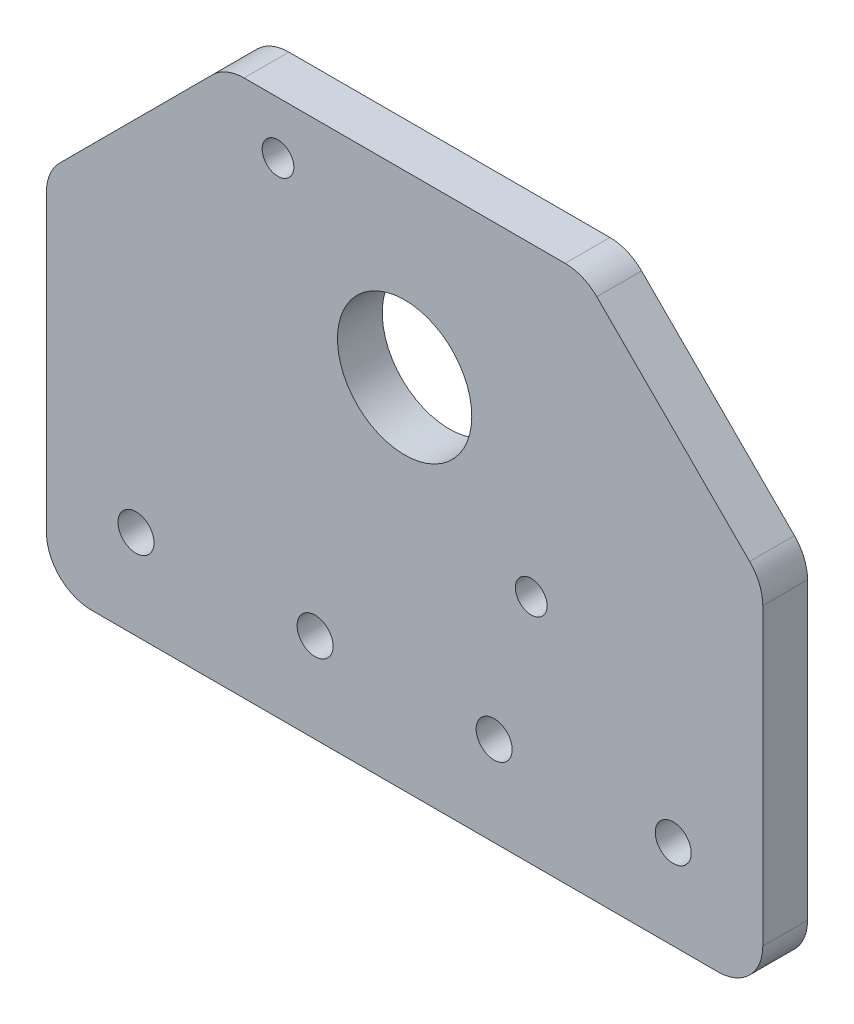
SolidWorks part; units mm, degrees
material "6061-T6 (SS)"
ref_plane "Front Plane" through (0, 0, 0) normal (0, 0, 1) x (1, 0, 0)
ref_plane "Top Plane" through (0, 0, 0) normal (0, 1, 0) x (1, 0, 0)
ref_plane "Right Plane" through (0, 0, 0) normal (1, 0, 0) x (0, 0, -1)
sketch "Sketch1" plane through (0, 0, 0) normal (0, 0, 1) x (1, 0, 0)
  line L0 (50.8, 25.4) -> (-50.8, 25.4)
  line L1 (-50.8, 25.4) -> (-50.8, -50.8)
  line L2 (-50.8, -50.8) -> (50.8, -50.8)
  line L3 (50.8, -50.8) -> (50.8, 25.4)
  circle A0 centre (0, 0) radius 9.525
  point P4 (0, -50.8)
  dimension "D1" = 19.05
  dimension "D2" = 25.4
  dimension "D3" = 76.2
  dimension "D4" = 101.6
extrude "Boss-Extrude1" add sketch "Sketch1" along normal mid plane 6.35
hole_wizard "#8 Clearance Hole1" positions "Sketch3" profile "Sketch2" hole size "#8" standard "ANSI Inch" end condition through all
sketch "Sketch3" plane through (0, 0, 3.175) normal (0, 0, 1) x (1, 0, 0)
  line L0 (-17.9605, 17.9605) -> (17.9605, -17.9605) construction
  line L2 (-50.8, -50.8) -> (50.8, -50.8) construction
  point P0 (-17.9605, 17.9605)
  point P2 (17.9605, -17.9605)
  dimension "D1" = 50.8
  dimension "D2" = 45
sketch "Sketch2" plane through (-17.9605, 17.9605, 3.175) normal (1, 0, 0) x (0, -1, 0)
  line L0 (0, 0) -> (0, 6.35)
  line L1 (0, 6.35) -> (2.2479, 6.35)
  line L2 (2.2479, 6.35) -> (2.2479, 0)
  line L5 (2.2479, 0) -> (0, 0)
  line L11 (0, -6.35) -> (0, 107.95) construction
  dimension "Thru Hole Dia." = 4.4958
  dimension "Thru Hole Depth" = 6.35
chamfer "Chamfer1" distance 25.4 angle 45 2 edges at (50.8, 25.4, 0) (-50.8, 25.4, 0)
hole_wizard "#10 Clearance Hole2" positions "Sketch5" profile "Sketch4" hole size "#10" standard "ANSI Inch" end condition through all
sketch "Sketch5" plane through (0, 0, 3.175) normal (0, 0, 1) x (1, 0, 0)
  line L0 (-50.8, -50.8) -> (50.8, -50.8) construction
  line L1 (-50.8, 0) -> (-50.8, -50.8) construction
  point P0 (-38.1, -38.1)
  point P12 (-12.7, -38.1)
  point P13 (12.7, -38.1)
  point P14 (38.1, -38.1)
  dimension "D1" = 12.7
  dimension "D2" = 12.7
  dimension "D4" = 25.4
  dimension "D3" = 4
sketch "Sketch4" plane through (-38.1, -38.1, 3.175) normal (1, 0, 0) x (0, -1, 0)
  line L0 (0, 0) -> (0, 6.35)
  line L1 (0, 6.35) -> (2.5527, 6.35)
  line L2 (2.5527, 6.35) -> (2.5527, 0)
  line L5 (2.5527, 0) -> (0, 0)
  line L11 (0, -6.35) -> (0, 107.95) construction
  dimension "Thru Hole Dia." = 5.1054
  dimension "Thru Hole Depth" = 6.35
fillet "Fillet1" radius 6.35 6 edges at (50.8, -50.8, 0) (-50.8, -50.8, 0) (-50.8, 0, 0) (-25.4, 25.4, 0) (50.8, 0, 0) (25.4, 25.4, 0)
